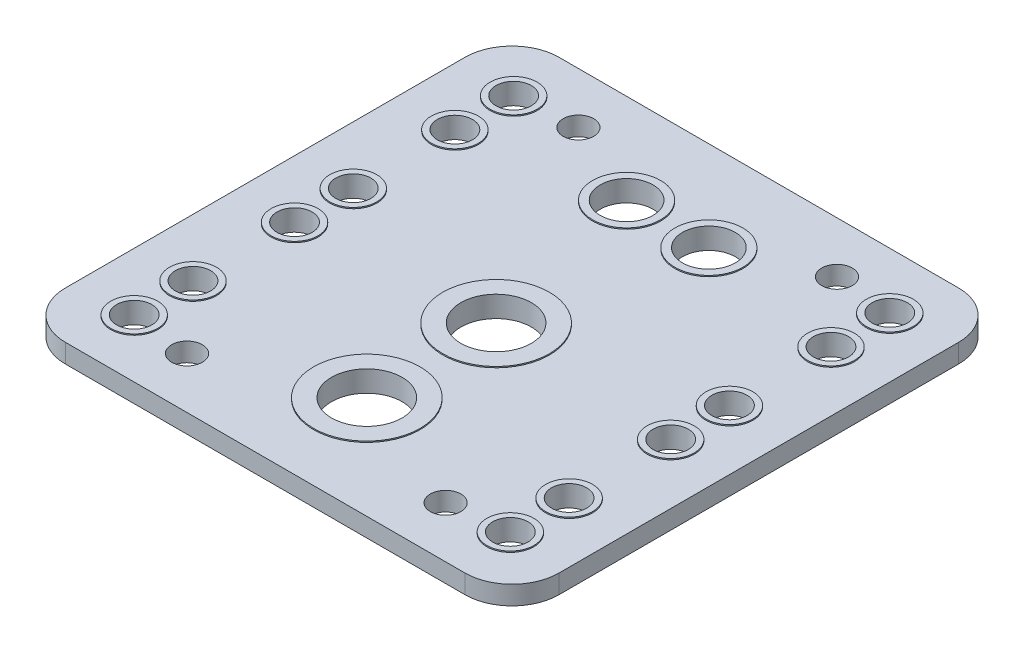
SolidWorks part; units mm, degrees
ref_plane "Alzado" through (0, 0, 0) normal (0, 0, 1) x (1, 0, 0)
ref_plane "Planta" through (0, 0, 0) normal (0, 1, 0) x (1, 0, 0)
ref_plane "Vista lateral" through (0, 0, 0) normal (1, 0, 0) x (0, 0, -1)
sketch "Croquis1" plane through (0, 0, 0) normal (0, 1, 0) x (1, 0, 0)
  line L1 (-17, 21) -> (17, 21)
  line L2 (-21, 17) -> (-21, -17)
  line L3 (-17, -21) -> (17, -21)
  line L4 (21, 17) -> (21, -17)
  line L5 (-21, 21) -> (21, -21) construction
  line L6 (-21, -21) -> (21, 21) construction
  arc A0 (17, 21) -> (21, 17) centre (17, 17) cw
  arc A1 (17, -21) -> (21, -17) centre (17, -17) ccw
  arc A2 (-21, -17) -> (-17, -21) centre (-17, -17) ccw
  arc A3 (-17, 21) -> (-21, 17) centre (-17, 17) ccw
  point P0 (0, 0)
  dimension "D1" = 4
  dimension "D2" = 42
  dimension "D3" = 42
extrude "Saliente-Extruir1" add sketch "Croquis1" along normal mid plane 1.6
sketch "Croquis2" plane through (0, 0.8, 0) normal (0, 1, 0) x (1, 0, 0)
  line L1 (11, -16.65) -> (-11, -16.65) construction
  line L2 (11, -16.65) -> (11, 16.65) construction
  line L3 (11, 16.65) -> (-11, 16.65) construction
  line L4 (-11, -16.65) -> (-11, 16.65) construction
  line L5 (11, -16.65) -> (-11, 16.65) construction
  line L6 (11, 16.65) -> (-11, -16.65) construction
  circle A0 centre (-11, 16.65) radius 1.3
  circle A1 centre (11, 16.65) radius 1.3
  circle A2 centre (11, -16.65) radius 1.3
  circle A3 centre (-11, -16.65) radius 1.3
  point P0 (0, 0)
  dimension "D1" = 2.6
  dimension "D2" = 33.3
  dimension "D3" = 22
extrude "Cortar-Extruir1" cut sketch "Croquis2" against normal through all both and the other way through all
sketch "Croquis3" plane through (0, 0.8, 0) normal (0, 1, 0) x (1, 0, 0)
  line L0 (0, -1.3521) -> (0, -12.3521) construction
  circle A0 centre (0, -12.3521) radius 3
  circle A1 centre (0, -1.3521) radius 3
  point P4 (0, -1.3521)
  dimension "D1" = 6
  dimension "D2" = 11
extrude "Cortar-Extruir2" cut sketch "Croquis3" against normal through all
sketch "Croquis5" plane through (0, 0, 0) normal (0, 1, 0) x (1, 0, 0)
  circle A0 centre (0, -12.3521) radius 3
  circle A1 centre (0, -12.3521) radius 4.5337
  circle A2 centre (0, -1.3521) radius 3
  circle A3 centre (0, -1.3521) radius 4.5337
  circle A4 centre (0, -12.3521) radius 3 construction
extrude "Saliente-Extruir2" add sketch "Croquis5" along normal mid plane 1.8
sketch "Croquis6" plane through (0, 0.8, 0) normal (0, 1, 0) x (1, 0, 0)
  line L0 (-3.5, 13.25) -> (3.5, 13.25) construction
  line L1 (0, 23.1314) -> (0, -25.294) construction
  line L2 (-16, 16.14) -> (-16, 11.14) construction
  line L3 (-16, 2.5) -> (-16, -2.5) construction
  line L4 (-16, -11.14) -> (-16, -16.14) construction
  line L5 (-21, 17) -> (-21, -17) construction
  line L6 (17, 21) -> (-17, 21) construction
  line L7 (-17, -21) -> (17, -21) construction
  circle A0 centre (-3.5, 13.25) radius 2.25
  circle A1 centre (3.5, 13.25) radius 2.25
  circle A2 centre (-16, 2.5) radius 1.5
  circle A3 centre (-16, -2.5) radius 1.5
  circle A4 centre (-16, 11.14) radius 1.5
  circle A5 centre (-16, 16.14) radius 1.5
  circle A6 centre (-16, -11.14) radius 1.5
  circle A7 centre (-16, -16.14) radius 1.5
  circle A8 centre (16, -16.14) radius 1.5
  circle A9 centre (16, -11.14) radius 1.5
  circle A10 centre (16, 16.14) radius 1.5
  circle A11 centre (16, 11.14) radius 1.5
  circle A12 centre (16, -2.5) radius 1.5
  circle A13 centre (16, 2.5) radius 1.5
  point P4 (0, 13.25)
  point P32 (-16, 0)
  dimension "D1" = 3
  dimension "D8" = 4.5
  dimension "D2" = 5
  dimension "D3" = 5
  dimension "D4" = 5
  dimension "D5" = 5
  dimension "D6" = 4.86
  dimension "D7" = 4.86
  dimension "D9" = 7
  dimension "D10" = 7.75
extrude "Cortar-Extruir3" cut sketch "Croquis6" against normal through all
sketch "Croquis7" plane through (0, 0, 0) normal (0, 1, 0) x (1, 0, 0)
  line L0 (0, 6.6749) -> (0, -3.6027) construction
  circle A0 centre (-16, -16.14) radius 1.5
  circle A1 centre (-16, -11.14) radius 1.5
  circle A2 centre (-16, -2.5) radius 1.5
  circle A3 centre (-16, 2.5) radius 1.5
  circle A4 centre (-16, 11.14) radius 1.5
  circle A5 centre (-16, 16.14) radius 1.5
  circle A6 centre (-16, 16.14) radius 1.5 construction
  circle A7 centre (-16, 16.14) radius 2
  circle A8 centre (-16, 11.14) radius 2
  circle A9 centre (-16, 2.5) radius 2
  circle A10 centre (-16, -2.5) radius 2
  circle A11 centre (-16, -16.14) radius 2
  circle A12 centre (-16, -11.14) radius 2
  circle A13 centre (-3.5, 13.25) radius 2.25
  circle A14 centre (-3.5, 13.25) radius 2.8949
  circle A15 centre (3.5, 13.25) radius 2.8949
  circle A16 centre (3.5, 13.25) radius 2.25
  circle A17 centre (16, -11.14) radius 2
  circle A18 centre (16, -16.14) radius 2
  circle A19 centre (16, -2.5) radius 2
  circle A20 centre (16, 2.5) radius 2
  circle A21 centre (16, 11.14) radius 2
  circle A22 centre (16, 16.14) radius 2
  circle A23 centre (16, 16.14) radius 1.5
  circle A24 centre (16, 11.14) radius 1.5
  circle A25 centre (16, 2.5) radius 1.5
  circle A26 centre (16, -2.5) radius 1.5
  circle A27 centre (16, -11.14) radius 1.5
  circle A28 centre (16, -16.14) radius 1.5
  dimension "D1" = 4
extrude "Saliente-Extruir3" add sketch "Croquis7" along normal mid plane 1.8
